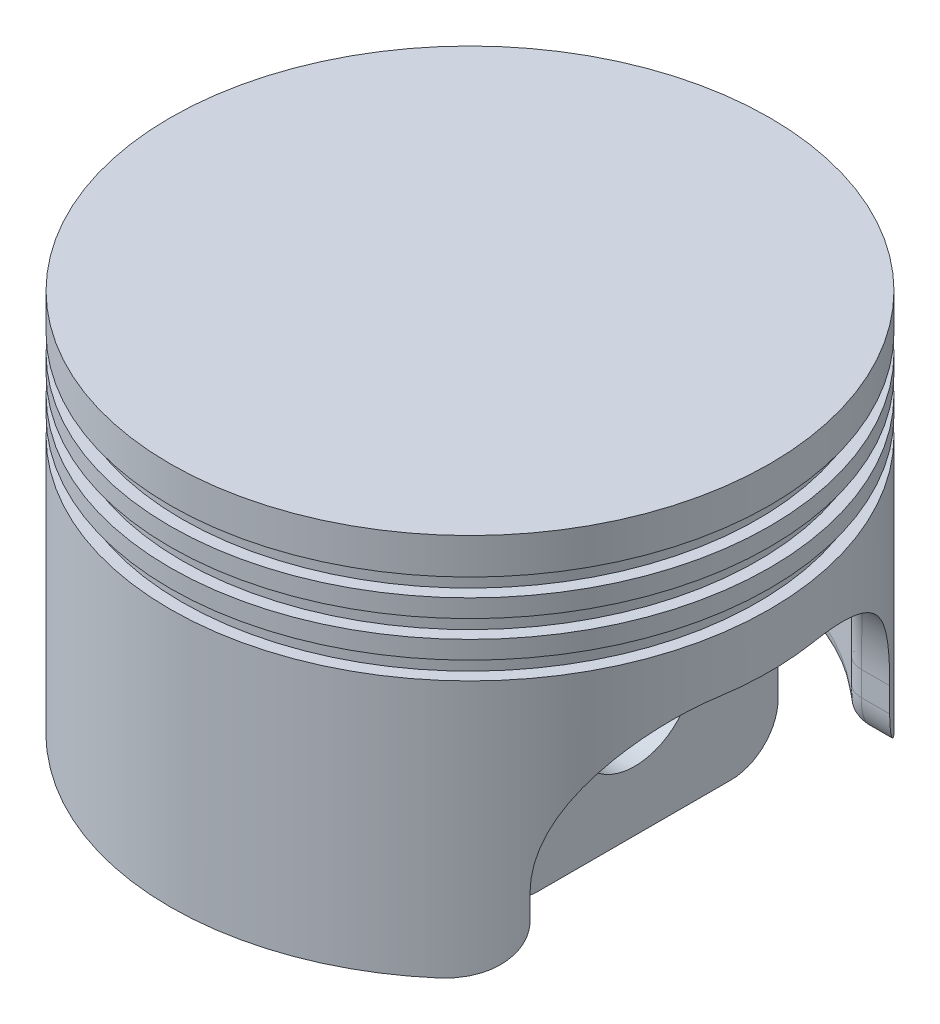
SolidWorks part; units mm, degrees
ref_plane "Front Plane" through (0, 0, 0) normal (0, 0, 1) x (1, 0, 0)
ref_plane "Top Plane" through (0, 0, 0) normal (0, 1, 0) x (1, 0, 0)
ref_plane "Right Plane" through (0, 0, 0) normal (1, 0, 0) x (0, 0, -1)
sketch "Sketch1" plane through (0, 0, 0) normal (0, 0, 1) x (1, 0, 0)
  line L0 (0, 0) -> (63.5, 0)
  line L1 (63.5, 0) -> (63.5, -81.28)
  line L2 (63.5, -81.28) -> (57.15, -81.28)
  line L3 (57.15, -81.28) -> (57.15, -19)
  line L4 (57.15, -19) -> (0, -19)
  line L5 (0, -19) -> (0, 0)
  dimension "D1" = 63.5
  dimension "D2" = 81.28
  dimension "D3" = 19
  dimension "D4" = 57.15
revolve "Revolve1" add sketch "Sketch1" angle 360 about L5
sketch "Sketch2" plane through (0, 0, 0) normal (1, 0, 0) x (0, 0, -1)
  line L0 (-63.5, -81.28) -> (63.5, -81.28) construction
  line L1 (-38.1, -38.1) -> (38.1, -38.1)
  line L2 (-38.1, -38.1) -> (-38.1, -124.46)
  line L3 (-38.1, -124.46) -> (38.1, -124.46)
  line L4 (38.1, -38.1) -> (38.1, -124.46)
  line L5 (-38.1, -38.1) -> (38.1, -124.46) construction
  line L6 (-38.1, -124.46) -> (38.1, -38.1) construction
  point P0 (0, -81.28)
  dimension "D1" = 43.18
  dimension "D2" = 76.2
extrude "Cut-Extrude1" cut sketch "Sketch2" against normal through all both and the other way through all
sketch "Sketch3" plane through (0, 0, 0) normal (1, 0, 0) x (0, 0, -1)
  line L0 (63.5, -81.28) -> (63.5, 0) construction
  line L1 (60.96, -7.62) -> (66.04, -7.62)
  line L2 (60.96, -7.62) -> (60.96, -11.43)
  line L3 (60.96, -11.43) -> (66.04, -11.43)
  line L4 (66.04, -7.62) -> (66.04, -11.43)
  line L5 (60.96, -7.62) -> (66.04, -11.43) construction
  line L6 (60.96, -11.43) -> (66.04, -7.62) construction
  line L7 (63.5, 0) -> (-63.5, 0) construction
  line L8 (0, 0) -> (0, 22.0865) construction
  point P0 (63.5, -9.525)
  dimension "D1" = 3.81
  dimension "D2" = 7.62
  dimension "D3" = 2.54
revolve "Cut-Revolve1" cut sketch "Sketch3" angle 360 about L8
pattern_linear "LPattern1" count 3 spacing 7.62 along (0, -1, 0) of "Cut-Revolve1"
sketch "Sketch4" plane through (0, -19, 0) normal (0, -1, 0) x (1, 0, 0)
  line L0 (0, 0) -> (0, 47.8374) construction
  line L1 (-34.88, 30.4) -> (-15.88, 30.4)
  line L2 (-34.88, 30.4) -> (-34.88, -30.4)
  line L3 (-34.88, -30.4) -> (-15.88, -30.4)
  line L4 (-15.88, 30.4) -> (-15.88, -30.4)
  line L5 (-34.88, 30.4) -> (-15.88, -30.4) construction
  line L6 (-34.88, -30.4) -> (-15.88, 30.4) construction
  line L7 (34.88, -30.4) -> (15.88, -30.4)
  line L8 (34.88, 30.4) -> (15.88, 30.4)
  line L9 (15.88, 30.4) -> (15.88, -30.4)
  line L10 (34.88, 30.4) -> (34.88, -30.4)
  point P0 (-25.38, 0)
  point P7 (-15.88, 0)
  point P8 (-34.88, 0)
  dimension "D1" = 19
  dimension "D2" = 60.8
  dimension "D3" = 31.76
extrude "Boss-Extrude1" add sketch "Sketch4" along normal blind 63.5
sketch "Sketch5" plane through (34.88, 0, 0) normal (1, 0, 0) x (0, 0, -1)
  line L0 (30.4, -82.5) -> (-30.4, -82.5) construction
  circle A0 centre (0, -57.1) radius 12.7
  dimension "D1" = 25.4
  dimension "D2" = 25.4
extrude "Cut-Extrude2" cut sketch "Sketch5" against normal through all both
fillet "Fillet1" radius 28 4 edges at (-46.6985, -38.1, -38.1) (-46.6985, -38.1, 38.1) (46.6985, -38.1, -38.1) (46.6985, -38.1, 38.1)
fillet "Fillet2" radius 10 8 edges at (-46.6985, -81.28, -38.1) (46.6985, -81.28, -38.1) (46.6985, -81.28, 38.1) (-46.6985, -81.28, 38.1) (-25.38, -82.5, -30.4) (-25.38, -82.5, 30.4) (25.38, -82.5, -30.4) (25.38, -82.5, 30.4)
fillet "Fillet3" radius 5 16 edges at (41.3657, -76.2692, 39.4335) (42.5971, -68.69, 38.1) (50.4318, -43.6881, 26.8841) (57.15, -38.1, 0) (46.055, -51.2516, -33.8387) (42.5971, -68.69, -38.1) (40.0022, -78.1316, -40.816) (0, -81.28, -57.15) (-41.3657, -76.2692, -39.4335) (-42.5971, -68.69, -38.1) (-50.4318, -43.6881, -26.8841) (-57.15, -38.1, 0) (-46.055, -51.2516, 33.8387) (-42.5971, -68.69, 38.1) (-40.0022, -78.1316, 40.816) (0, -81.28, 57.15)
fillet "Fillet4" radius 5 1 edges at (0, -19, -57.15)
